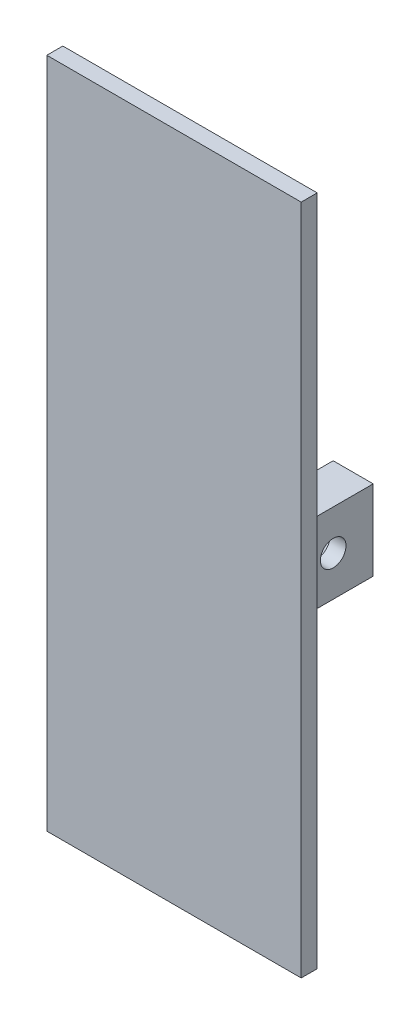
SolidWorks part; units mm, degrees
ref_plane "Front Plane" through (0, 0, 0) normal (0, 0, 1) x (1, 0, 0)
ref_plane "Top Plane" through (0, 0, 0) normal (0, 1, 0) x (1, 0, 0)
ref_plane "Right Plane" through (0, 0, 0) normal (1, 0, 0) x (0, 0, -1)
sketch "Sketch1" plane through (0, 0, 0) normal (0, 0, 1) x (1, 0, 0)
  line L1 (15.9, -42) -> (-15.9, -42)
  line L2 (15.9, -42) -> (15.9, 42)
  line L3 (15.9, 42) -> (-15.9, 42)
  line L4 (-15.9, -42) -> (-15.9, 42)
  line L5 (15.9, -42) -> (-15.9, 42) construction
  line L6 (15.9, 42) -> (-15.9, -42) construction
  point P0 (0, 0)
  dimension "D1" = 84
  dimension "D2" = 31.8
extrude "Boss-Extrude1" add sketch "Sketch1" along normal blind 2
sketch "Sketch2" plane through (0, 0, 0) normal (0, 0, -1) x (-1, 0, 0)
  line L0 (-15.9, -42) -> (-15.9, 42) construction
  line L1 (13.9, -39.95) -> (-13.9, -39.95)
  line L2 (13.9, -39.95) -> (13.9, 39.95)
  line L3 (13.9, 39.95) -> (-13.9, 39.95)
  line L4 (-13.9, -39.95) -> (-13.9, 39.95)
  line L5 (13.9, -39.95) -> (-13.9, 39.95) construction
  line L6 (13.9, 39.95) -> (-13.9, -39.95) construction
  point P0 (0, 0)
  dimension "D1" = 79.9
  dimension "D2" = 2
extrude "Boss-Extrude2" add sketch "Sketch2" along normal blind 0.001
sketch "Sketch3" plane through (0, 0, 0) normal (0, 0, -1) x (-1, 0, 0)
  line L0 (-13.9, -39.95) -> (-13.9, 39.95) construction
  line L1 (-13.9, 5) -> (-8.9, 5)
  line L2 (-13.9, 5) -> (-13.9, -5)
  line L3 (-13.9, -5) -> (-8.9, -5)
  line L4 (-8.9, 5) -> (-8.9, -5)
  dimension "D1" = 5
  dimension "D2" = 10
  dimension "D3" = 5
extrude "Boss-Extrude3" add sketch "Sketch3" along normal blind 9
sketch "Sketch4" plane through (8.9, 0, 0) normal (-1, 0, 0) x (0, 0, 1)
  line L0 (-9, 5) -> (-0.001, 5) construction
  line L1 (-2.3834, 2.8) -> (-5.6166, 2.8)
  line L2 (-5.6166, 2.8) -> (-7.2332, 0)
  line L3 (-7.2332, 0) -> (-5.6166, -2.8)
  line L4 (-5.6166, -2.8) -> (-2.3834, -2.8)
  line L5 (-2.3834, -2.8) -> (-0.7668, 0)
  line L6 (-0.7668, 0) -> (-2.3834, 2.8)
  line L8 (2, 42) -> (2, -42) construction
  circle A0 centre (-4, 0) radius 2.8 construction
  dimension "D1" = 5.6
  dimension "D2" = 6
extrude "Cut-Extrude1" cut sketch "Sketch4" against normal blind 3
sketch "Sketch5" plane through (11.9, 0, 0) normal (-1, 0, 0) x (0, 0, 1)
  line L1 (-9, 5) -> (-0.001, 5) construction
  line L2 (0, -5) -> (0, 5) construction
  circle A0 centre (-4, 0) radius 1.6
  dimension "D1" = 4
  dimension "D2" = 5
  dimension "D3" = 3.2
extrude "Cut-Extrude2" cut sketch "Sketch5" against normal up to surface (2 mm away) up to face at (13.9, 0, -2.2505)
